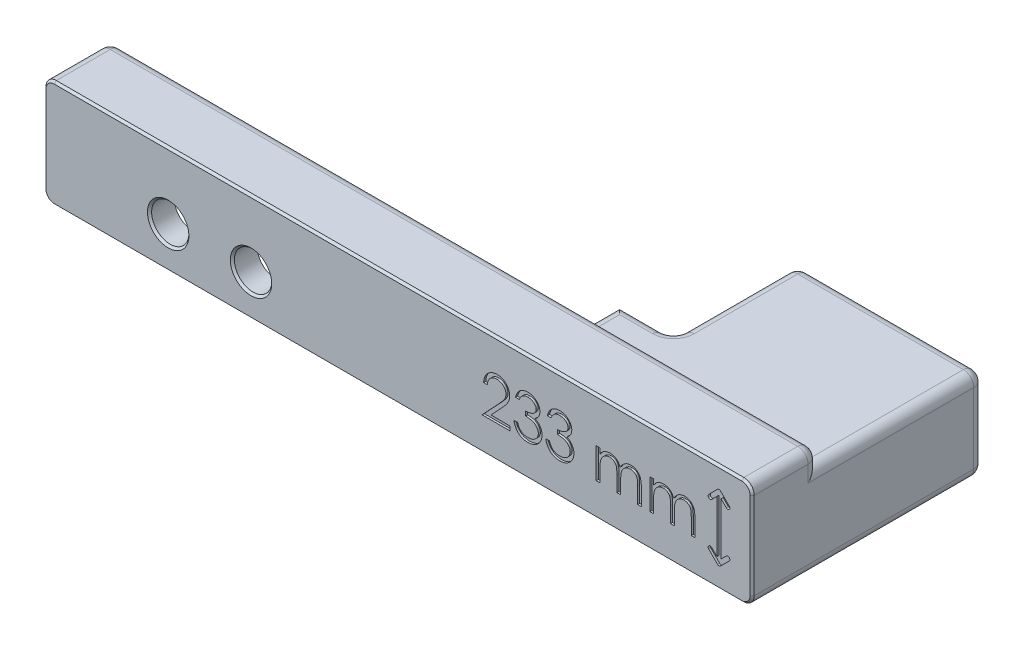
SolidWorks part; units mm, degrees
ref_plane "Front Plane" through (0, 0, 0) normal (0, 0, 1) x (1, 0, 0)
ref_plane "Top Plane" through (0, 0, 0) normal (0, 1, 0) x (1, 0, 0)
ref_plane "Right Plane" through (0, 0, 0) normal (1, 0, 0) x (0, 0, -1)
sketch "main_features_sketch" plane through (0, 0, 0) normal (0, 0, 1) x (1, 0, 0)
  line L0 (24, 290) -> (0, 290) construction
  line L1 (0, 300) -> (0, 0) construction
  line L2 (107, 300) -> (107, 0) construction
  line L3 (0, 300) -> (107, 300)
  line L4 (0, 300) -> (0, 280)
  line L5 (0, 280) -> (107, 280)
  line L6 (107, 300) -> (107, 280)
  line L7 (0, 280) -> (-6, 280)
  line L8 (-6, 280) -> (-6, 306)
  line L9 (-6, 306) -> (113, 306)
  line L10 (113, 306) -> (113, 280)
  line L11 (113, 280) -> (107, 280)
  line L12 (0, 300) -> (0, 306) construction
  line L13 (113, 280) -> (165, 280)
  line L14 (165, 280) -> (165, 302.05)
  line L15 (165, 302.05) -> (113, 302.05)
  line L17 (120, 280) -> (120, 302.05)
  line L18 (117, 632.0963) -> (117, -1823.9037) construction
  line L19 (113, 306) -> (165, 306)
  line L20 (165, 306) -> (165, 302.05)
  line L21 (113, 302.05) -> (107, 302.05)
  line L23 (107, 302.05) -> (107, 300)
  circle A0 centre (24, 290) radius 3.1
  circle A1 centre (44, 290) radius 3.1
  line M24 (67.2, 300) -> (1, 300)
  line M25 (1, 300) -> (1, 0)
  line M27 (67.2, 0) -> (67.2, 300)
  circle M35 centre (24, 290) radius 4.5
  circle M39 centre (44, 290) radius 4.5
  dimension "D1" = 6.2
  dimension "D2" = 6
  dimension "D3" = 45
  dimension "D4" = 3
  dimension "D5" = 22.05
extrude "base" add sketch "main_features_sketch" along normal blind 6 contours L5 M25 M27 M24 M35 M39 | L11 L10 L9 L8 L7 L4 L3 L6 M24 | L6 L3 L5 M27 | L20 L19 L10 L15 | L17 L13 L14 L15 | L13 L17 L15 L10 | L4 L5 L3 M25 | L21 L23 L6 L11 L10 region at (44.4031, 301.1311, 0) region at (0.5, 290, 0) region at (34.1106, 290, 0) region at (87.1, 290, 0) region at (110, 291.025, 0) region at (139, 304.025, 0) region at (116.5, 291.025, 0) region at (142.5, 291.025, 0)
extrude "ledge" add sketch "main_features_sketch<3>" against normal blind 10 contours L11 L10 L9 L8 L7 L4 L3 L6 M24 | L20 L19 L10 L15 region at (44.4031, 301.1311, 0) region at (139, 304.025, 0)
sketch "main_features_sketch<3>" plane through (0, 0, 0) normal (0, 0, 1) x (1, 0, 0) same geometry as "main_features_sketch"
extrude "Boss-Extrude3" add sketch "main_features_sketch<4>" against normal blind 20 contours L21 L23 L6 L11 L10 | L13 L17 L15 L10 region at (110, 291.025, 0) region at (116.5, 291.025, 0)
sketch "main_features_sketch<4>" plane through (0, 0, 0) normal (0, 0, 1) x (1, 0, 0) same geometry as "main_features_sketch"
extrude "Boss-Extrude4" add sketch "main_features_sketch<5>" against normal blind 50 contours L17 L13 L14 L15 region at (142.5, 291.025, 0)
sketch "main_features_sketch<5>" plane through (0, 0, 0) normal (0, 0, 1) x (1, 0, 0) same geometry as "main_features_sketch"
fillet "Fillet1" radius 2.5 20 edges at (113.5, 280, -20) (113.5, 302.05, -20) (142.5, 280, -50) (165, 291.025, -50) (142.5, 302.05, -50) (120, 291.025, -50) (165, 304.025, -10) (79.5, 306, -10) (-6, 293, -10) (0, 280, -5) (120, 291.025, -20) (120, 302.05, -35) (107, 302.05, -15) (120, 280, -35) (107, 280, -10) (-6, 280, -2) (-6, 306, -2) (165, 306, -2) (165, 302.05, -30) (165, 280, -22)
chamfer "Chamfer1" distance 0.5 angle 45 10 edges at (48.5, 290, 6) (28.5, 290, 6) (-5.2678, 305.2678, 6) (79.5, 306, 6) (164.2678, 305.2678, 6) (165, 293, 6) (164.2678, 280.7322, 6) (79.5, 280, 6) (-5.2678, 280.7322, 6) (-6, 293, 6)
sketch "Sketch3" plane through (0, 0, 6) normal (0, 0, 1) x (1, 0, 0)
  line L1 (157, 300.5) -> (157, 285.5)
  line L2 (157, 285.5) -> (154.8787, 287.6213)
  line L3 (157, 285.5) -> (159.1213, 287.6213)
  line L4 (157, 300.5) -> (154.8787, 298.3787)
  line L5 (157, 300.5) -> (159.1213, 298.3787)
  line L6 (165, 293) -> (157, 293) construction
  line L7 (165, 303.5) -> (165, 282.5) construction
  line L8 (156.6464, 300.8536) -> (154.5251, 298.7322)
  line L9 (156.5, 300.5) -> (156.5, 285.5)
  line L10 (156.6464, 300.1464) -> (158.7678, 298.0251)
  line L11 (157.3536, 285.1464) -> (159.4749, 287.2678)
  line L12 (157.3536, 285.8536) -> (155.2322, 287.9749)
  line L13 (157.3536, 300.1464) -> (155.2322, 298.0251)
  line L14 (157.5, 300.5) -> (157.5, 285.5)
  line L15 (157.3536, 300.8536) -> (159.4749, 298.7322)
  line L16 (156.6464, 285.8536) -> (158.7678, 287.9749)
  line L17 (156.6464, 285.1464) -> (154.5251, 287.2678)
  arc A0 (156.6464, 300.8536) -> (157.3536, 300.1464) centre (157, 300.5) cw
  arc A1 (154.5251, 298.7322) -> (155.2322, 298.0251) centre (154.8787, 298.3787) ccw
  arc A2 (156.5, 300.5) -> (157.5, 300.5) centre (157, 300.5) cw
  arc A3 (156.5, 285.5) -> (157.5, 285.5) centre (157, 285.5) ccw
  arc A4 (156.6464, 300.1464) -> (157.3536, 300.8536) centre (157, 300.5) cw
  arc A5 (158.7678, 298.0251) -> (159.4749, 298.7322) centre (159.1213, 298.3787) ccw
  arc A6 (157.3536, 285.1464) -> (156.6464, 285.8536) centre (157, 285.5) cw
  arc A7 (159.4749, 287.2678) -> (158.7678, 287.9749) centre (159.1213, 287.6213) ccw
  arc A8 (157.3536, 285.8536) -> (156.6464, 285.1464) centre (157, 285.5) cw
  arc A9 (155.2322, 287.9749) -> (154.5251, 287.2678) centre (154.8787, 287.6213) ccw
  dimension "D1" = 15
  dimension "D2" = 3
  dimension "D3" = 8
  dimension "D4" = 0.5
  dimension "D5" = 0.5
extrude "Cut-Extrude1" cut sketch "Sketch3" against normal blind 0.5 contours L17 A9 L12 A8 | L16 A7 L11 A6 | L14 A3 L9 A2 | L15 A5 L10 A4 | L8 A1 L13 A0
sketch "Sketch4" plane through (0, 0, 6) normal (0, 0, 1) x (1, 0, 0)
  line L0 (99.3981, 288) -> (165, 288) construction
  line L1 (165, 303.5) -> (165, 282.5) construction
  text T0 "233 mm" font "Century Gothic" height 10
  point P10 (165, 293)
  dimension "D1" = 5
extrude "Cut-Extrude2" cut sketch "Sketch4" against normal blind 0.5
